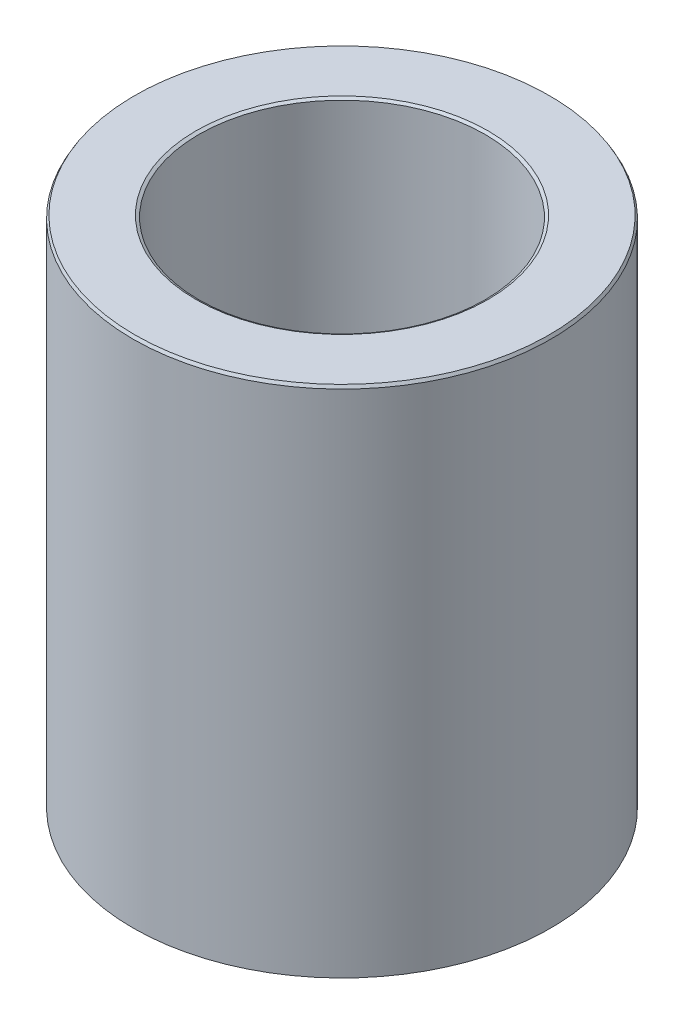
SolidWorks part; units mm, degrees
ref_plane "Front Plane" through (0, 0, 0) normal (0, 0, 1) x (1, 0, 0)
ref_plane "Top Plane" through (0, 0, 0) normal (0, 1, 0) x (1, 0, 0)
ref_plane "Right Plane" through (0, 0, 0) normal (1, 0, 0) x (0, 0, -1)
sketch "Sketch1" plane through (0, 0, 0) normal (0, 1, 0) x (1, 0, 0)
  circle A0 centre (0, 0) radius 47.5
  dimension "SLEEVE_OD" = 95
extrude "Boss-Extrude1" add sketch "Sketch1" along normal blind 116.9836
sketch "Sketch2" plane through (0, 0, 0) normal (0, 1, 0) x (1, 0, 0)
  circle A0 centre (0, 0) radius 32.5502
  dimension "BORE_D" = 65.1005
extrude "Cut-Extrude1" cut sketch "Sketch2" along normal through all
chamfer "Chamfer1" distance 0.6608 angle 30 4 edges at (0, 116.9836, 32.5502) (0, 0, 32.5502) (0, 0, 47.5) (0, 116.9836, 47.5) first distance on face at (0, 116.9836, 32.5502) first distance on face at (0, 0, 32.5502) first distance on face at (0, 116.9836, 47.5)
